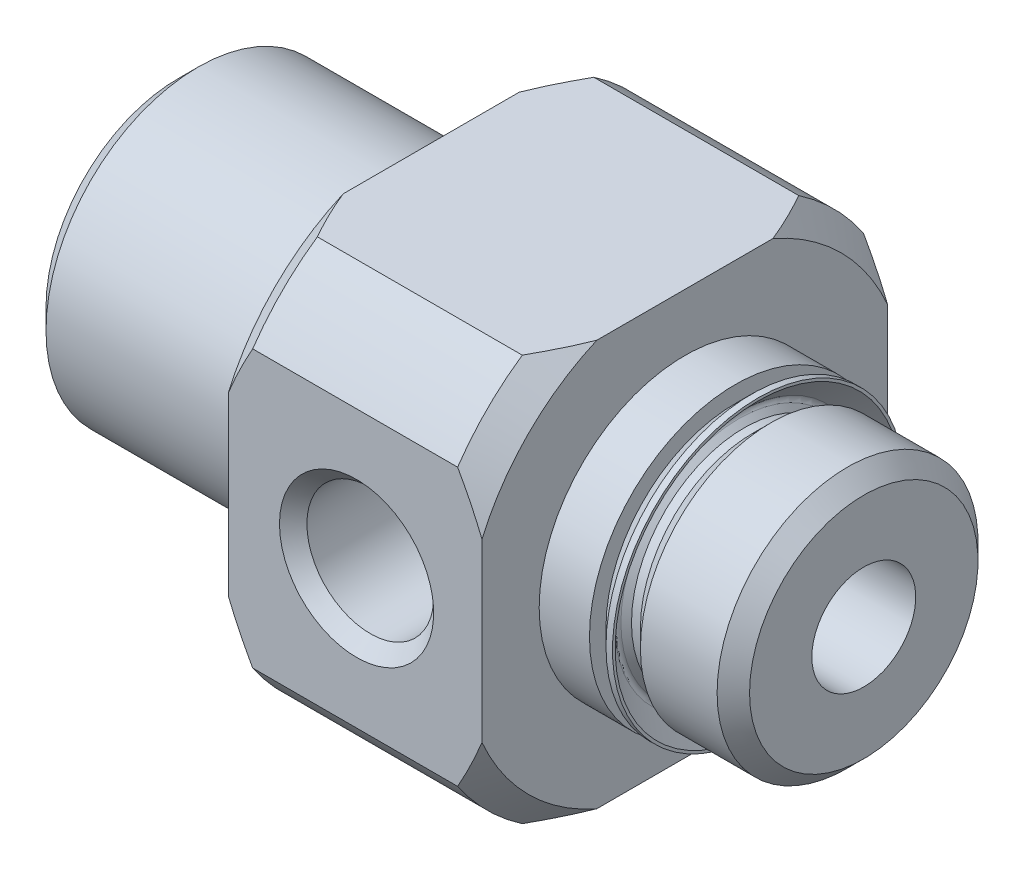
SolidWorks part; units mm, degrees
ref_plane "Front Plane" through (0, 0, 0) normal (0, 0, 1) x (1, 0, 0)
ref_plane "Top Plane" through (0, 0, 0) normal (0, 1, 0) x (1, 0, 0)
ref_plane "Right Plane" through (0, 0, 0) normal (1, 0, 0) x (0, 0, -1)
sketch "Sketch1" plane through (0, 0, 0) normal (0, 0, 1) x (1, 0, 0)
  line L0 (0, 0) -> (0, 4.1326)
  line L1 (0, 4.1326) -> (0.6299, 4.7625)
  line L2 (0.6299, 4.7625) -> (7.9248, 4.7625)
  line L3 (7.9248, 4.7625) -> (7.9248, 0)
  line L4 (7.9248, 0) -> (0, 0)
  line L5 (7.9248, 0) -> (0, 0) construction
revolve "Revolve1" add sketch "Sketch1" angle 360 about L5 reverse direction yes
cosmetic thread "Cosmetic Thread1" parameters "D1"=7.9248, "D2"=8.2652
sketch "Sketch2" plane through (0, 0, 0) normal (0, 0, 1) x (1, 0, 0)
  line L0 (7.9248, 0) -> (7.9248, 6.9215)
  line L1 (7.9248, 6.9215) -> (8.6868, 7.6835)
  line L2 (8.6868, 7.6835) -> (15.1003, 7.6835)
  line L3 (15.1003, 7.6835) -> (15.8623, 6.9215)
  line L4 (15.8623, 6.9215) -> (15.8623, 3.5242)
  line L5 (15.8623, 3.5242) -> (17.9959, 3.5242)
  line L6 (17.9959, 3.5242) -> (18.5547, 4.0831)
  line L7 (18.5547, 4.0831) -> (20.955, 4.0831)
  line L8 (20.955, 4.0831) -> (21.463, 3.5751)
  line L9 (21.463, 3.5751) -> (21.463, 0)
  line L10 (21.463, 0) -> (7.9248, 0)
  line L11 (21.463, 0) -> (7.9248, 0) construction
revolve "Revolve2" add sketch "Sketch2" angle 360 about L11 reverse direction yes
sketch "Sketch3" plane through (0, 0, 0) normal (0, 0, 1) x (1, 0, 0)
  line L0 (15.8623, 0) -> (15.8623, 4.5593)
  line L1 (15.8623, 4.5593) -> (17.4371, 4.5593)
  line L2 (17.4371, 4.5593) -> (17.4371, 0)
  line L3 (17.4371, 0) -> (15.8623, 0)
  line L4 (17.4371, 0) -> (15.8623, 0) construction
revolve "Revolve3" add sketch "Sketch3" angle 360 about L4 reverse direction yes
sketch "Sketch4" plane through (0, 0, 0) normal (0, 0, 1) x (1, 0, 0)
  line L0 (0, 0) -> (0, 2.0066)
  line L1 (0, 2.0066) -> (0.381, 1.6256)
  line L2 (0.381, 1.6256) -> (21.463, 1.6256)
  line L3 (21.463, 1.6256) -> (21.463, 0)
  line L4 (21.463, 0) -> (0, 0)
  line L5 (21.463, 0) -> (0, 0) construction
revolve "Cut-Revolve1" cut sketch "Sketch4" angle 360 about L5 reverse direction yes
sketch "Sketch5" plane through (0, 0, 0) normal (1, 0, 0) x (0, 0, -1)
  line L0 (-12.7, -12.7) -> (12.7, -12.7)
  line L1 (12.7, -12.7) -> (12.7, 12.7)
  line L2 (12.7, 12.7) -> (-12.7, 12.7)
  line L3 (-12.7, 12.7) -> (-12.7, -12.7)
  line L4 (-6.35, -6.35) -> (6.35, -6.35)
  line L5 (6.35, -6.35) -> (6.35, 6.35)
  line L6 (6.35, 6.35) -> (-6.35, 6.35)
  line L7 (-6.35, 6.35) -> (-6.35, -6.35)
extrude "Cut-Extrude1" cut sketch "Sketch5" along normal blind 21.463
sketch "Sketch6" plane through (0, 0, 0) normal (0, 1, 0) x (1, 0, 0)
  line L0 (11.938, 0) -> (13.9217, 0)
  line L1 (13.9217, 0) -> (13.9217, -5.9207)
  line L2 (13.9217, -5.9207) -> (14.351, -6.35)
  line L3 (14.351, -6.35) -> (11.938, -6.35)
  line L4 (11.938, -6.35) -> (11.938, 0)
  line L5 (11.938, -6.35) -> (11.938, 0) construction
revolve "Cut-Revolve2" cut sketch "Sketch6" angle 360 about L5 reverse direction yes
cosmetic thread "Cosmetic Thread2" parameters "D1"=4.4069, "D2"=4.826
ref_plane "Plane1" through (15.0876, 0, 0) normal (1, 0, 0) x (0, 0, -1)
ref_plane "Plane2" through (15.0876, 0, 0) normal (1, 0, 0) x (0, 0, -1)
ref_plane "Plane3" through (0, 0, 0) normal (0, -0.7071, 0.7071) x (1, 0, 0)
ref_plane "Plane4" through (0, 0, 0) normal (1, 0, 0) x (0, 0, -1)
ref_plane "Plane5" through (15.8623, 0, 0) normal (1, 0, 0) x (0, 0, -1)
ref_plane "Plane6" through (7.9248, 0, 0) normal (1, 0, 0) x (0, 0, -1)
ref_plane "Plane7" through (15.8623, 0, 0) normal (1, 0, 0) x (0, 0, -1)
sketch "Sketch7" plane through (0, 0, 0) normal (0, 0, 1) x (1, 0, 0)
  line L0 (17.4371, 4.0431) -> (17.4371, 3.2703)
  line L1 (17.4371, 3.2703) -> (17.9959, 3.2703)
  line L2 (17.9959, 3.2703) -> (17.9959, 3.5242)
  line L3 (17.9959, 3.5242) -> (17.7165, 3.5242)
  line L4 (17.7165, 3.5242) -> (17.5509, 3.6899)
  line L5 (17.5509, 3.8695) -> (18.1565, 4.4751)
  line L6 (18.1565, 4.4751) -> (18.1565, 4.5593)
  line L7 (18.1565, 4.5593) -> (17.9533, 4.5593)
  line L8 (17.9533, 4.5593) -> (17.4371, 4.0431)
  line L9 (17.9959, 0) -> (17.4371, 0) construction
  arc A0 (17.5509, 3.6899) -> (17.5509, 3.8695) centre (17.6407, 3.7797) cw
revolve "Revolve4" add sketch "Sketch7" angle 360 about L9 reverse direction yes
ref_plane "Plane8" through (17.9959, 0, 0) normal (1, 0, 0) x (0, 0, -1)
ref_plane "Plane9" through (7.9248, 0, 0) normal (1, 0, 0) x (0, 0, -1)
ref_plane "Plane10" through (7.9248, 0, 0) normal (1, 0, 0) x (0, 0, -1)
ref_plane "Plane11" through (0, 6.35, 0) normal (0, 1, 0) x (1, 0, 0)
ref_plane "Plane12" through (0, -6.35, 0) normal (0, 1, 0) x (1, 0, 0)
ref_plane "Plane13" through (7.9248, 0, 0) normal (1, 0, 0) x (0, 0, -1)
ref_plane "Plane14" through (0, 0, 0) normal (0, 0, 1) x (1, 0, 0)
ref_plane "Plane15" through (0, 0, 0) normal (0, 1, 0) x (1, 0, 0)
ref_plane "Plane16" through (0, 0, 0) normal (0, 1, 0) x (1, 0, 0)
ref_plane "Plane17" through (0, 0, 0) normal (0, 1, 0) x (1, 0, 0)
ref_plane "Plane18" through (0, 0, 0) normal (1, 0, 0) x (0, 0, -1)
ref_plane "hh XY" through (0, 0, 0) normal (0, 0, 1) x (1, 0, 0)
ref_plane "hh XZ" through (0, 4.7625, 0) normal (0, -1, 0) x (-1, 0, 0)
ref_plane "hh YZ" through (0, 0, 0) normal (1, 0, 0) x (0, 0, -1)
ref_axis "hh X" through (-80.9, 4.7625, 0) along (1, 0, 0)
ref_axis "hh Y" through (0, -50, 0) along (0, 1, 0)
ref_axis "hh Z" through (0, 4.7625, 80.9) along (0, 0, -1)
sketch3d "hh"
  point P0 (0, 4.7625, 0)
ref_plane "port XY" through (0, 0, 0) normal (0, 0, 1) x (1, 0, 0)
ref_plane "port XZ" through (0, 0, 0) normal (0, -1, 0) x (-1, 0, 0)
ref_plane "port YZ" through (11.938, 0, 0) normal (1, 0, 0) x (0, 0, -1)
ref_axis "port X" through (-80.9, 0, 0) along (1, 0, 0)
ref_axis "port Y" through (11.938, -50, 0) along (0, 1, 0)
ref_axis "port Z" through (11.938, 0, 80.9) along (0, 0, -1)
sketch3d "port"
  point P0 (11.938, 0, 0)
ref_plane "rod_guide XY" through (0, 0, 0) normal (1, 0, 0) x (0, 0, -1)
ref_plane "rod_guide XZ" through (0, 0, 0) normal (0, -1, 0) x (-1, 0, 0)
ref_plane "rod_guide YZ" through (0, 0, 0) normal (0, 0, -1) x (-1, 0, 0)
ref_axis "rod_guide X" through (0, 0, 80.9) along (0, 0, -1)
ref_axis "rod_guide Y" through (0, -50, 0) along (0, 1, 0)
ref_axis "rod_guide Z" through (80.9, 0, 0) along (-1, 0, 0)
sketch3d "rod_guide"
  point P0 (0, 0, 0)
ref_plane "sq1 XY" through (0, 0, 0) normal (1, 0, 0) x (0, 0, -1)
ref_plane "sq1 XZ" through (0, 0, 0) normal (0, -1, 0) x (-1, 0, 0)
ref_plane "sq1 YZ" through (0, 0, 6.35) normal (0, 0, -1) x (-1, 0, 0)
ref_axis "sq1 X" through (0, 0, 80.9) along (0, 0, -1)
ref_axis "sq1 Y" through (0, -50, 6.35) along (0, 1, 0)
ref_axis "sq1 Z" through (80.9, 0, 6.35) along (-1, 0, 0)
sketch3d "sq1"
  point P0 (0, 0, 6.35)
ref_plane "sq2 XY" through (0, 0, 0) normal (1, 0, 0) x (0, 0, -1)
ref_plane "sq2 XZ" through (0, 0, 0) normal (0, -1, 0) x (-1, 0, 0)
ref_plane "sq2 YZ" through (0, 0, -6.35) normal (0, 0, -1) x (-1, 0, 0)
ref_axis "sq2 X" through (0, 0, 80.9) along (0, 0, -1)
ref_axis "sq2 Y" through (0, -50, -6.35) along (0, 1, 0)
ref_axis "sq2 Z" through (80.9, 0, -6.35) along (-1, 0, 0)
sketch3d "sq2"
  point P0 (0, 0, -6.35)
ref_plane "t1 XY" through (7.9248, 0, 0) normal (1, 0, 0) x (0, 0, -1)
ref_plane "t1 XZ" through (0, 0, 0) normal (0, -1, 0) x (-1, 0, 0)
ref_plane "t1 YZ" through (0, 0, 0) normal (0, 0, -1) x (-1, 0, 0)
ref_axis "t1 X" through (7.9248, 0, 80.9) along (0, 0, -1)
ref_axis "t1 Y" through (7.9248, -50, 0) along (0, 1, 0)
ref_axis "t1 Z" through (80.9, 0, 0) along (-1, 0, 0)
sketch3d "t1"
  point P0 (7.9248, 0, 0)
ref_plane "t111 XY" through (7.9248, 0, 0) normal (1, 0, 0) x (0, 0, -1)
ref_plane "t111 XZ" through (0, 0, 0) normal (0, -1, 0) x (-1, 0, 0)
ref_plane "t111 YZ" through (0, 0, 0) normal (0, 0, -1) x (-1, 0, 0)
ref_axis "t111 X" through (7.9248, 0, 80.9) along (0, 0, -1)
ref_axis "t111 Y" through (7.9248, -50, 0) along (0, 1, 0)
ref_axis "t111 Z" through (80.9, 0, 0) along (-1, 0, 0)
sketch3d "t111"
  point P0 (7.9248, 0, 0)
ref_plane "to_foot_bracket XY" through (7.9248, 0, 0) normal (1, 0, 0) x (0, 0, -1)
ref_plane "to_foot_bracket XZ" through (0, 0, 0) normal (0, -1, 0) x (-1, 0, 0)
ref_plane "to_foot_bracket YZ" through (0, 0, 0) normal (0, 0, -1) x (-1, 0, 0)
ref_axis "to_foot_bracket X" through (7.9248, 0, 80.9) along (0, 0, -1)
ref_axis "to_foot_bracket Y" through (7.9248, -50, 0) along (0, 1, 0)
ref_axis "to_foot_bracket Z" through (80.9, 0, 0) along (-1, 0, 0)
sketch3d "to_foot_bracket"
  point P0 (7.9248, 0, 0)
ref_plane "to_nut XY" through (7.9248, 0, 0) normal (1, 0, 0) x (0, 0, -1)
ref_plane "to_nut XZ" through (0, 0, 0) normal (0, -1, 0) x (-1, 0, 0)
ref_plane "to_nut YZ" through (0, 0, 0) normal (0, 0, -1) x (-1, 0, 0)
ref_axis "to_nut X" through (7.9248, 0, 80.9) along (0, 0, -1)
ref_axis "to_nut Y" through (7.9248, -50, 0) along (0, 1, 0)
ref_axis "to_nut Z" through (80.9, 0, 0) along (-1, 0, 0)
sketch3d "to_nut"
  point P0 (7.9248, 0, 0)
ref_plane "to_rod XY" through (0, 0, 0) normal (1, 0, 0) x (0, 0, -1)
ref_plane "to_rod XZ" through (0, 0, 0) normal (0, -1, 0) x (-1, 0, 0)
ref_plane "to_rod YZ" through (0, 0, 0) normal (0, 0, -1) x (-1, 0, 0)
ref_axis "to_rod X" through (0, 0, 80.9) along (0, 0, -1)
ref_axis "to_rod Y" through (0, -50, 0) along (0, 1, 0)
ref_axis "to_rod Z" through (80.9, 0, 0) along (-1, 0, 0)
sketch3d "to_rod"
  point P0 (0, 0, 0)
ref_plane "to_screw XY" through (0, 0, 0) normal (0, 1, 0) x (1, 0, 0)
ref_plane "to_screw XZ" through (0, 0, 0) normal (0, 0, 1) x (1, 0, 0)
ref_plane "to_screw YZ" through (11.938, 0, 0) normal (1, 0, 0) x (0, 0, -1)
ref_axis "to_screw X" through (-80.9, 0, 0) along (1, 0, 0)
ref_axis "to_screw Y" through (11.938, 0, 50) along (0, 0, -1)
ref_axis "to_screw Z" through (11.938, 50, 0) along (0, -1, 0)
sketch3d "to_screw"
  point P0 (11.938, 0, 0)
ref_plane "to_trunnion_brackets XY" through (0, 0, 0) normal (0, 1, 0) x (1, 0, 0)
ref_plane "to_trunnion_brackets XZ" through (0, 0, 0) normal (0, 0, 1) x (1, 0, 0)
ref_plane "to_trunnion_brackets YZ" through (0, 0, 0) normal (1, 0, 0) x (0, 0, -1)
ref_axis "to_trunnion_brackets X" through (-80.9, 0, 0) along (1, 0, 0)
ref_axis "to_trunnion_brackets Y" through (0, 0, 50) along (0, 0, -1)
ref_axis "to_trunnion_brackets Z" through (0, 50, 0) along (0, -1, 0)
sketch3d "to_trunnion_brackets"
  point P0 (0, 0, 0)
ref_plane "to_trunnion_brackets1 XY" through (0, 6.35, 0) normal (0, 1, 0) x (1, 0, 0)
ref_plane "to_trunnion_brackets1 XZ" through (0, 0, 0) normal (0, 0, 1) x (1, 0, 0)
ref_plane "to_trunnion_brackets1 YZ" through (0, 0, 0) normal (1, 0, 0) x (0, 0, -1)
ref_axis "to_trunnion_brackets1 X" through (-80.9, 6.35, 0) along (1, 0, 0)
ref_axis "to_trunnion_brackets1 Y" through (0, 6.35, 50) along (0, 0, -1)
ref_axis "to_trunnion_brackets1 Z" through (0, 50, 0) along (0, -1, 0)
sketch3d "to_trunnion_brackets1"
  point P0 (0, 6.35, 0)
ref_plane "to_trunnion_brackets2 XY" through (0, -6.35, 0) normal (0, 1, 0) x (1, 0, 0)
ref_plane "to_trunnion_brackets2 XZ" through (0, 0, 0) normal (0, 0, 1) x (1, 0, 0)
ref_plane "to_trunnion_brackets2 YZ" through (0, 0, 0) normal (1, 0, 0) x (0, 0, -1)
ref_axis "to_trunnion_brackets2 X" through (-80.9, -6.35, 0) along (1, 0, 0)
ref_axis "to_trunnion_brackets2 Y" through (0, -6.35, 50) along (0, 0, -1)
ref_axis "to_trunnion_brackets2 Z" through (0, 50, 0) along (0, -1, 0)
sketch3d "to_trunnion_brackets2"
  point P0 (0, -6.35, 0)
ref_plane "to_tube XY" through (17.9959, 0, 0) normal (1, 0, 0) x (0, 0, -1)
ref_plane "to_tube XZ" through (0, 0, 0) normal (0, -1, 0) x (-1, 0, 0)
ref_plane "to_tube YZ" through (0, 0, 0) normal (0, 0, -1) x (-1, 0, 0)
ref_axis "to_tube X" through (17.9959, 0, 80.9) along (0, 0, -1)
ref_axis "to_tube Y" through (17.9959, -50, 0) along (0, 1, 0)
ref_axis "to_tube Z" through (80.9, 0, 0) along (-1, 0, 0)
sketch3d "to_tube"
  point P0 (17.9959, 0, 0)
